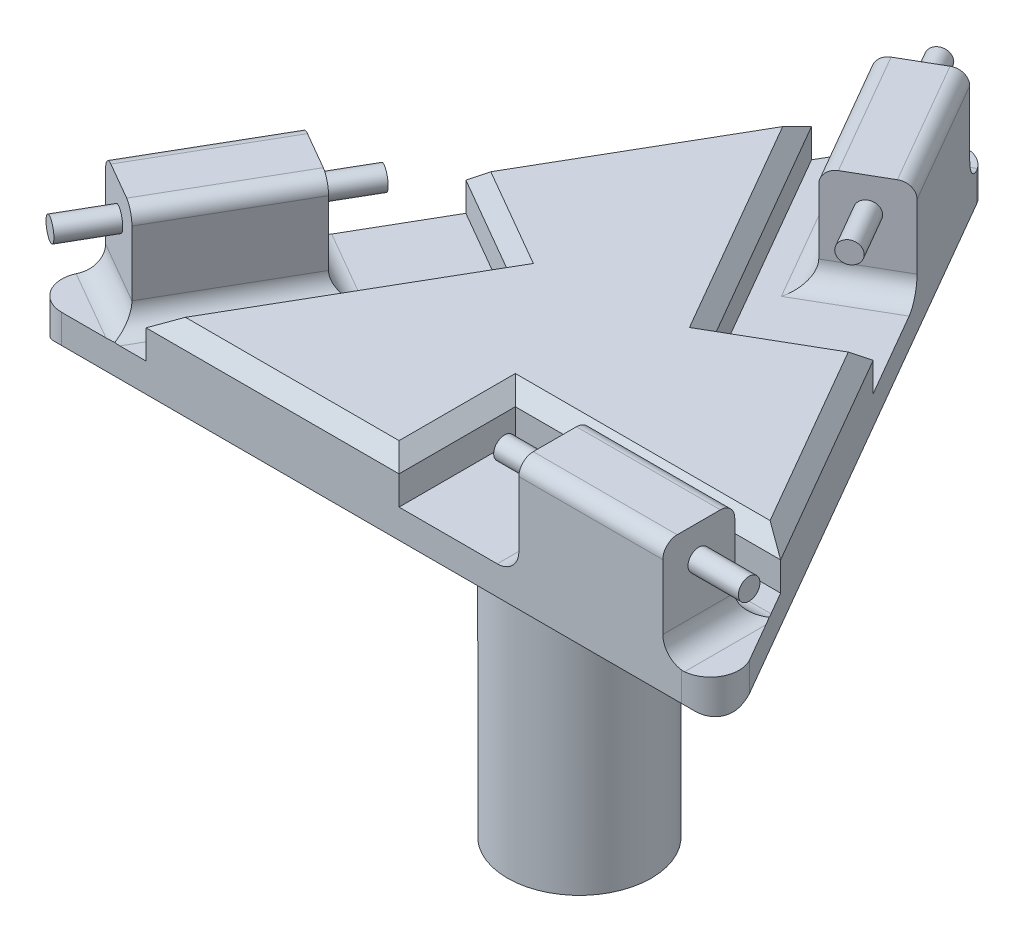
SolidWorks part; units mm, degrees
material "ABS"
ref_plane "Front Plane" through (0, 0, 0) normal (0, 0, 1) x (1, 0, 0)
ref_plane "Top Plane" through (0, 0, 0) normal (0, 1, 0) x (1, 0, 0)
ref_plane "Right Plane" through (0, 0, 0) normal (1, 0, 0) x (0, 0, -1)
sketch "Sketch1" plane through (0, 0, 0) normal (0, 1, 0) x (1, 0, 0)
  line L1 (0, 57.735) -> (-50, -28.8675)
  line L2 (-50, -28.8675) -> (50, -28.8675)
  line L3 (50, -28.8675) -> (0, 57.735)
  dimension "D1" = 100
extrude "Boss-Extrude1" add sketch "Sketch1" along normal blind 12
sketch "Sketch2" plane through (0, 12, 0) normal (0, 1, 0) x (1, 0, 0)
  line L0 (23.094, 17.735) -> (9.1023, 9.6569)
  line L1 (50, -28.8675) -> (0, 57.735) construction
  line L2 (9.1023, 9.6569) -> (-9.3278, 41.5788)
  line L3 (0, 57.735) -> (-50, -28.8675) construction
  line L4 (-9.3278, 41.5788) -> (0, 57.735)
  line L5 (0, 57.735) -> (23.094, 17.735)
  line L6 (-50, -28.8675) -> (-31.34, -28.8675)
  line L7 (-50, -28.8675) -> (50, -28.8675) construction
  line L8 (-31.34, -28.8675) -> (-12.911, 3.0525)
  line L9 (-12.911, 3.0525) -> (-26.906, 11.1325)
  line L10 (-26.906, 11.1325) -> (-50, -28.8675)
  line L11 (50, -28.8675) -> (40.67, -12.7075)
  line L12 (40.67, -12.7075) -> (3.81, -12.7075)
  line L13 (3.81, -12.7075) -> (3.81, -28.8675)
  line L14 (3.81, -28.8675) -> (50, -28.8675)
  dimension "D1" = 40
  dimension "D2" = 40
  dimension "D3" = 18.66
  dimension "D4" = 16.16
  dimension "D5" = 46.188
  dimension "D6" = 46.188
  dimension "D7" = 18.6556
  dimension "D8" = 16.1562
  dimension "D9" = 36.8602
  dimension "D10" = 36.858
  dimension "D11" = 18.66
  dimension "D12" = 46.19
  dimension "D13" = 16.16
  dimension "D14" = 36.86
extrude "Cut-Extrude2" cut sketch "Sketch2" against normal blind 6
sketch "Sketch5" plane through (0, 6, 0) normal (0, 1, 0) x (1, 0, 0)
  line L0 (6.109, 27.154) -> (14.7692, 32.154)
  line L1 (6.109, 27.154) -> (-3.891, 44.4745)
  line L2 (14.7692, 32.154) -> (4.7692, 49.4745)
  line L3 (-3.891, 44.4745) -> (4.7692, 49.4745)
  line L4 (23.094, 17.735) -> (0, 57.735) construction
  line L5 (-45.23, -20.6056) -> (-36.5697, -25.6056)
  line L6 (-26.906, 11.1325) -> (-50, -28.8675) construction
  line L7 (-36.5697, -25.6056) -> (-26.5697, -8.2851)
  line L8 (-26.5697, -8.2851) -> (-35.23, -3.2851)
  line L9 (-35.23, -3.2851) -> (-45.23, -20.6056)
  line L11 (40.46, -28.8675) -> (40.46, -18.8675)
  line L12 (3.81, -28.8675) -> (50, -28.8675) construction
  line L13 (40.46, -18.8675) -> (20.46, -18.8675)
  line L14 (20.46, -18.8675) -> (20.46, -28.8675)
  line L15 (20.46, -28.8675) -> (40.46, -28.8675)
  dimension "D1" = 20
  dimension "D2" = 10
  dimension "D3" = 20
  dimension "D4" = 10
  dimension "D5" = 9.54
  dimension "D6" = 9.5385
  dimension "D7" = 16.648
  dimension "D8" = 16.6495
  dimension "D9" = 20
  dimension "D10" = 10
  dimension "D11" = 9.54
  dimension "D12" = 16.65
extrude "Boss-Extrude2" add sketch "Sketch5" along normal blind 14
fillet "Fillet2" radius 2 1 edges at (9.7692, 20, -40.8142)
fillet "Fillet3" radius 2 1 edges at (1.109, 20, -35.8142)
fillet "Fillet4" radius 2 4 edges at (30.46, 20, 18.8675) (30.46, 20, 28.8675) (-40.23, 20, 11.9454) (-31.5697, 20, 16.9454)
chamfer "Chamfer1" distance 2 angle 45 3 edges at (25, 0, -14.4338) (-25, 0, -14.4338) (0, 0, 28.8675)
chamfer "Chamfer2" distance 2 angle 45 9 edges at (-18.1169, 12, -26.3557) (-0.1127, 12, -25.6179) (16.0982, 12, -13.696) (31.882, 12, -2.5138) (22.24, 12, 12.7075) (3.81, 12, 20.7875) (-13.765, 12, 28.8675) (-22.1255, 12, 12.9075) (-19.9085, 12, -7.0925)
fillet "Fillet5" radius 4 6 edges at (48.2679, 1, 27.8675) (-48.2679, 1, 27.8675) (0, 1, -55.735) (0, 4, -57.735) (50, 4, 28.8675) (-50, 4, 28.8675)
fillet "Fillet6" radius 3 9 edges at (40.46, 6, 23.8675) (30.46, 6, 18.8675) (20.46, 6, 23.8675) (0.4391, 6, -46.9745) (1.109, 6, -35.8142) (10.4391, 6, -29.654) (-30.8999, 6, 5.7851) (-31.5697, 6, 16.9454) (-40.8999, 6, 23.1056)
sketch "Sketch6" plane through (-10.2308, 0, -17.7202) normal (0.5, 0, 0.866) x (0.866, 0, -0.5)
  line L0 (18.8675, 18) -> (18.8675, 9) construction
  line L1 (28.8675, 18) -> (28.8675, 9) construction
  line L4 (18.8675, 9) -> (28.8675, 9) construction
  circle A0 centre (23.8675, 15.5) radius 1.5
  dimension "D1" = 3
  dimension "D2" = 5
  dimension "D3" = 5
  dimension "D4" = 6.5
extrude "Boss-Extrude4" add sketch "Sketch6" along normal blind 7
sketch "Sketch8" plane through (-20.2308, 0, -35.0407) normal (-0.5, 0, -0.866) x (-0.866, 0, 0.5)
  line L0 (-28.8675, 9) -> (-18.8675, 9) construction
  line L1 (-18.8675, 18) -> (-18.8675, 9) construction
  circle A0 centre (-23.8675, 15.5) radius 1.5
  dimension "D1" = 3
  dimension "D2" = 6.5
  dimension "D3" = 5
extrude "Boss-Extrude5" add sketch "Sketch8" along normal blind 7
sketch "Sketch9" plane through (40.46, 0, 0) normal (1, 0, 0) x (0, 0, -1)
  line L0 (-28.8675, 9) -> (-18.8675, 9) construction
  line L1 (-28.8675, 18) -> (-28.8675, 9) construction
  circle A0 centre (-23.8675, 15.5) radius 1.5
  dimension "D1" = 3
  dimension "D2" = 6.5
  dimension "D3" = 5
extrude "Boss-Extrude6" add sketch "Sketch9" along normal blind 7
sketch "Sketch10" plane through (20.46, 0, 0) normal (-1, 0, 0) x (0, 0, 1)
  line L0 (28.8675, 18) -> (28.8675, 9) construction
  line L2 (18.8675, 9) -> (28.8675, 9) construction
  circle A0 centre (23.8675, 15.5) radius 1.5
  dimension "D1" = 3
  dimension "D2" = 5
  dimension "D3" = 6.5
extrude "Boss-Extrude7" add sketch "Sketch10" along normal blind 7
sketch "Sketch11" plane through (-20.23, 0, 35.0394) normal (-0.5, 0, 0.866) x (0.866, 0, 0.5)
  line L0 (-28.8675, 9) -> (-18.8675, 9) construction
  line L1 (-28.8675, 18) -> (-28.8675, 9) construction
  circle A0 centre (-23.8675, 15.5) radius 1.5
  dimension "D1" = 3
  dimension "D2" = 6.5
  dimension "D3" = 5
extrude "Boss-Extrude8" add sketch "Sketch11" along normal blind 7
sketch "Sketch12" plane through (-10.23, 0, 17.7189) normal (0.5, 0, -0.866) x (-0.866, 0, -0.5)
  line L0 (18.8675, 9) -> (28.8675, 9) construction
  line L1 (28.8675, 18) -> (28.8675, 9) construction
  circle A0 centre (23.8675, 15.5) radius 1.5
  dimension "D1" = 3
  dimension "D2" = 6.5
  dimension "D3" = 5
extrude "Boss-Extrude9" add sketch "Sketch12" along normal blind 7
sketch "Sketch13" plane through (0, 0, 0) normal (0, -1, 0) x (1, 0, 0)
  circle A0 centre (0, 0) radius 10
  dimension "D1" = 20
extrude "Boss-Extrude10" add sketch "Sketch13" along normal blind 50
fillet "Fillet7" radius 3 1 edges at (0, 0, 10)
